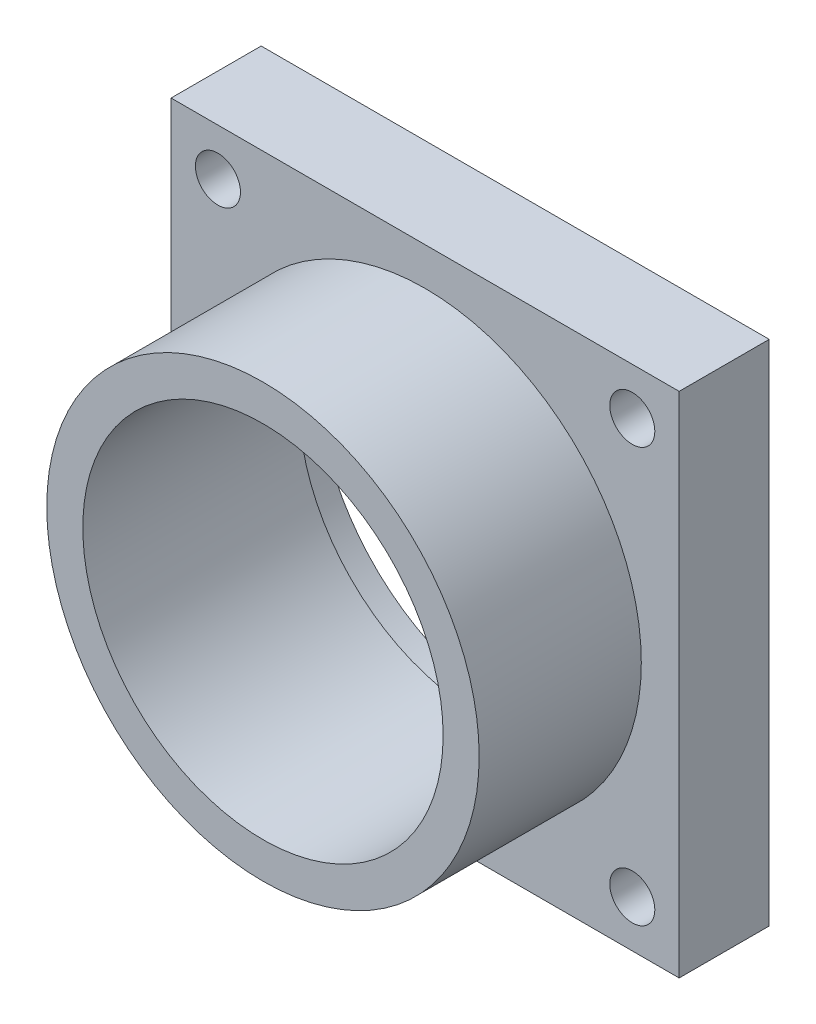
SolidWorks part; units mm, degrees
ref_plane "Front Plane" through (0, 0, 0) normal (0, 0, 1) x (1, 0, 0)
ref_plane "Top Plane" through (0, 0, 0) normal (0, 1, 0) x (1, 0, 0)
ref_plane "Right Plane" through (0, 0, 0) normal (1, 0, 0) x (0, 0, -1)
sketch "Sketch1" plane through (0, 0, 0) normal (0, 0, 1) x (1, 0, 0)
  line L0 (-14.1, 14.1) -> (14.1, 14.1)
  line L1 (-14.1, 14.1) -> (-14.1, -14.1)
  line L2 (-14.1, -14.1) -> (14.1, -14.1)
  line L3 (14.1, 14.1) -> (14.1, -14.1)
  line L4 (-11.5, 11.5) -> (11.5, 11.5) construction
  circle A0 centre (0, 0) radius 2.5
  circle A1 centre (-11.5, 11.5) radius 1.25
  circle A5 centre (0, 0) radius 11
  circle A6 centre (11.5, 11.5) radius 1.25
  circle A7 centre (11.5, -11.5) radius 1.25
  circle A8 centre (-11.5, -11.5) radius 1.25
  circle A9 centre (0, 0) radius 10
  circle A10 centre (0, 0) radius 12
  point P7 (0, 14.1)
  point P8 (-14.1, 0)
  dimension "D1" = 5
  dimension "D6" = 2.5
  dimension "D7" = 22
  dimension "D12" = 24
  dimension "D13" = 20
  dimension "D2" = 28.2
  dimension "D3" = 28.2
  dimension "D4" = 11.5
  dimension "D5" = 11.5
  dimension "D8" = 2
  dimension "D10" = 23
  dimension "D11" = 23
  dimension "D9" = 2
extrude "Boss-Extrude1" add sketch "Sketch1" along normal blind 5 contours L3 L0 L1 L2 A8 A7 A1 A10 A6 | L4 A10 A5 | A10 L4 | A5 A9 region at (0, 13.7012, 0) region at (0, 11.7004, 0) region at (0, 11.1641, 0) region at (-10.6889, 0, 0)
extrude "Boss-Extrude2" add sketch "Sketch1<3>" along normal blind 14 contours A5 A9 | L4 A10 A5 | A10 L4 region at (0, 11.7004, 0) region at (0, 11.1641, 0) region at (-10.6889, 0, 0)
sketch "Sketch1<3>" plane through (0, 0, 0) normal (0, 0, 1) x (1, 0, 0) same geometry as "Sketch1"
extrude "Cut-Extrude1" cut sketch "Sketch1<4>" along normal blind 2 contours A5 A9 region at (-10.6889, 0, 0)
sketch "Sketch1<4>" plane through (0, 0, 0) normal (0, 0, 1) x (1, 0, 0) same geometry as "Sketch1"
